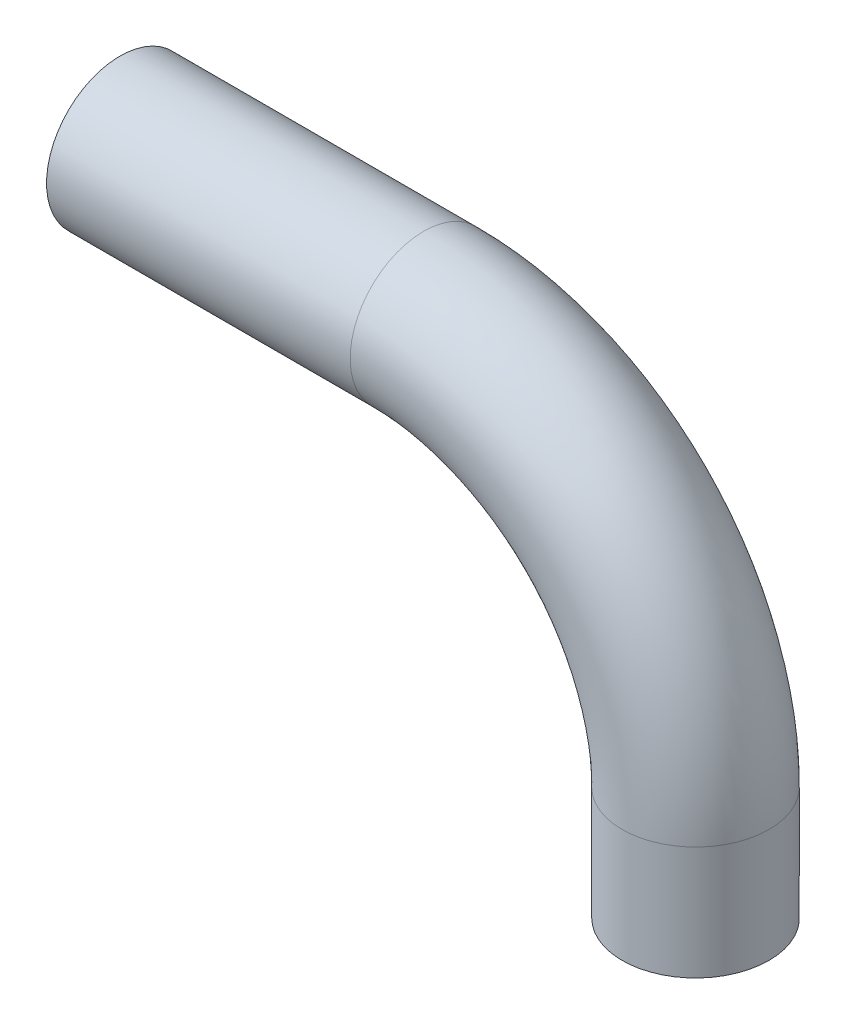
SolidWorks part; units mm, degrees
ref_plane "Front Plane" through (0, 0, 0) normal (0, 0, 1) x (1, 0, 0)
ref_plane "Top Plane" through (0, 0, 0) normal (0, 1, 0) x (1, 0, 0)
ref_plane "Right Plane" through (0, 0, 0) normal (1, 0, 0) x (0, 0, -1)
sketch "Sketch1" plane through (0, 0, 0) normal (0, 0, 1) x (1, 0, 0)
  line L0 (0, 0) -> (55.8225, 0)
  line L1 (105.8225, -50) -> (105.8225, -70.852)
  arc A0 (105.8225, -50) -> (55.8225, 0) centre (55.8225, -50) ccw
  point P3 (105.8225, -70.852)
  dimension "D1" = 50
sketch "Sketch2" plane through (0, 0, 0) normal (1, 0, 0) x (0, 0, -1)
  circle A0 centre (0, 0) radius 13.5
  dimension "D1" = 27
sweep "Sweep1" add profiles "Sketch2" path "Sketch1"
sketch "Sketch3" plane through (0, 0, 0) normal (-1, 0, 0) x (0, 0, 1)
  circle A0 centre (0, 0) radius 13.1
  dimension "D1" = 26.2
sweep "Cut-Sweep1" cut profiles "Sketch3" path "Sketch1<2>"
sketch "Sketch1<2>" plane through (0, 0, 0) normal (0, 0, 1) x (1, 0, 0) same geometry as "Sketch1"
